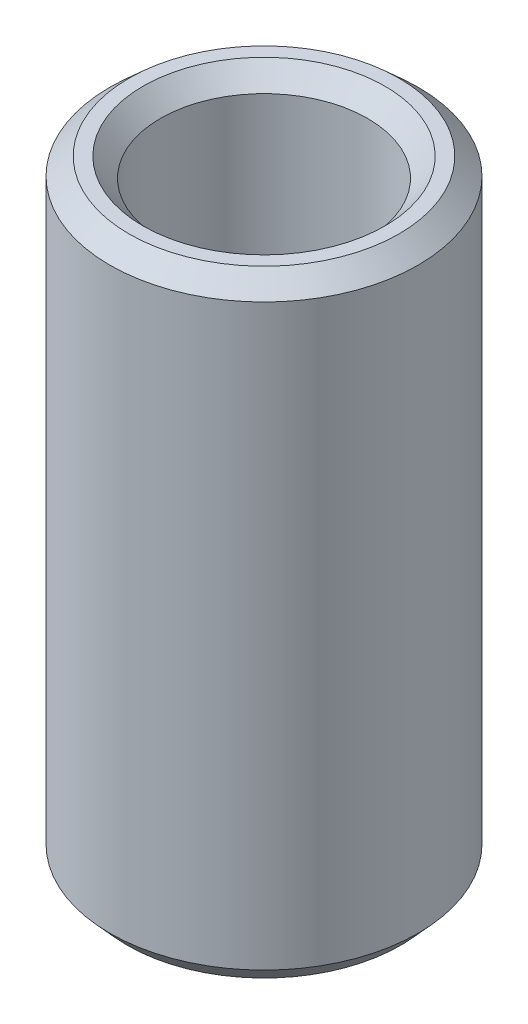
SolidWorks part; units mm, degrees
ref_plane "Front Plane" through (0, 0, 0) normal (0, 0, 1) x (1, 0, 0)
ref_plane "Top Plane" through (0, 0, 0) normal (0, 1, 0) x (1, 0, 0)
ref_plane "Right Plane" through (0, 0, 0) normal (1, 0, 0) x (0, 0, -1)
sketch "Sketch1" plane through (0, 0, 0) normal (0, 1, 0) x (1, 0, 0)
  circle A0 centre (0, 0) radius 30
  dimension "SLEEVE_OD" = 60
extrude "Boss-Extrude1" add sketch "Sketch1" along normal blind 119.7367
sketch "Sketch2" plane through (0, 0, 0) normal (0, 1, 0) x (1, 0, 0)
  circle A0 centre (0, 0) radius 20.1682
  dimension "BORE_D" = 40.3364
extrude "Cut-Extrude1" cut sketch "Sketch2" along normal through all
chamfer "Chamfer1" distance 3.3904 angle 47.769 4 edges at (0, 119.7367, 20.1682) (0, 0, 20.1682) (0, 0, 30) (0, 119.7367, 30) first distance on face at (0, 119.7367, 20.1682) first distance on face at (0, 0, 20.1682) first distance on face at (0, 119.7367, 30)
